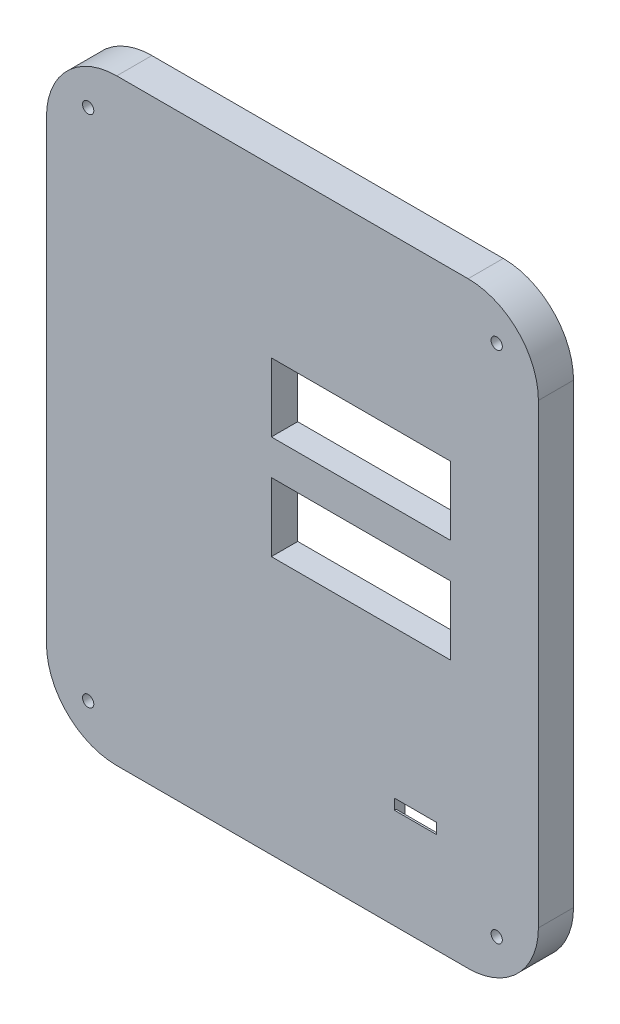
SolidWorks part; units mm, degrees
ref_plane "Front Plane" through (0, 0, 0) normal (0, 0, 1) x (1, 0, 0)
ref_plane "Top Plane" through (0, 0, 0) normal (0, 1, 0) x (1, 0, 0)
ref_plane "Right Plane" through (0, 0, 0) normal (1, 0, 0) x (0, 0, -1)
sketch "Sketch1" plane through (0, 0, 0) normal (0, 0, 1) x (1, 0, 0)
  line L0 (-47.1227, 101.0393) -> (52.8773, 101.0393) construction
  line L1 (72.8773, 81.0393) -> (72.8773, -48.9607) construction
  line L2 (-0.3727, -68.9607) -> (-47.1227, -68.9607) construction
  line L3 (-67.1227, -48.9607) -> (-67.1227, 81.0393) construction
  line L4 (-47.1227, 101.0393) -> (52.8773, 101.0393)
  line L5 (72.8773, 81.0393) -> (72.8773, -48.9607)
  line L6 (52.8773, -68.9607) -> (-47.1227, -68.9607)
  line L7 (-67.1227, -48.9607) -> (-67.1227, 81.0393)
  arc A0 (-47.1227, 101.0393) -> (-67.1227, 81.0393) centre (-47.1227, 81.0393) ccw construction
  arc A1 (72.8773, 81.0393) -> (52.8773, 101.0393) centre (52.8773, 81.0393) ccw construction
  arc A2 (52.8773, -68.9607) -> (72.8773, -48.9607) centre (52.8773, -48.9607) ccw construction
  arc A3 (-67.1227, -48.9607) -> (-47.1227, -68.9607) centre (-47.1227, -48.9607) ccw construction
  arc A4 (-47.1227, 101.0393) -> (-67.1227, 81.0393) centre (-47.1227, 81.0393) ccw
  arc A5 (72.8773, 81.0393) -> (52.8773, 101.0393) centre (52.8773, 81.0393) ccw
  arc A6 (52.8773, -68.9607) -> (72.8773, -48.9607) centre (52.8773, -48.9607) ccw
  arc A7 (-67.1227, -48.9607) -> (-47.1227, -68.9607) centre (-47.1227, -48.9607) ccw
extrude "Boss-Extrude1" add sketch "Sketch1" along normal blind 10
shell "Shell1" thickness 4 removed face at (2.8773, 16.0393, 0)
ref_plane "Plane1" through (0, 16.0393, 0) normal (0, 1, 0) x (1, 0, 0)
ref_plane "Plane2" through (2.8773, 0, 0) normal (1, 0, 0) x (0, 0, -1)
sketch "Sketch2" plane through (0, 0, 0) normal (0, 0, -1) x (-1, 0, 0)
  line L0 (47.89, 95.1878) -> (51.0972, 87.4483) construction
  line L1 (61.2712, 81.8066) -> (53.5317, 85.0139) construction
  line L2 (47.89, 95.1878) -> (51.0972, 87.4483)
  line L3 (61.2712, 81.8066) -> (53.5317, 85.0139)
  line L4 (-52.8773, 97.0393) -> (47.1227, 97.0393) construction
  line L5 (-52.8773, 97.0393) -> (47.1227, 97.0393)
  line L6 (63.1227, 81.0393) -> (63.1227, -48.9607) construction
  line L7 (63.1227, 81.0393) -> (63.1227, -48.9607)
  arc A0 (47.89, 95.1878) -> (45.1185, 97.0393) centre (45.1185, 94.0393) ccw construction
  arc A1 (51.0972, 87.4483) -> (53.5317, 85.0139) centre (55.2544, 89.1711) ccw construction
  arc A2 (63.1227, 79.0352) -> (61.2712, 81.8066) centre (60.1227, 79.0352) ccw construction
  arc A3 (47.89, 95.1878) -> (45.1185, 97.0393) centre (45.1185, 94.0393) ccw
  arc A4 (51.0972, 87.4483) -> (53.5317, 85.0139) centre (55.2544, 89.1711) ccw
  arc A5 (63.1227, 79.0352) -> (61.2712, 81.8066) centre (60.1227, 79.0352) ccw
  arc A6 (63.1227, 81.0393) -> (47.1227, 97.0393) centre (47.1227, 81.0393) ccw construction
  arc A7 (63.1227, 81.0393) -> (47.1227, 97.0393) centre (47.1227, 81.0393) ccw
  circle A8 centre (55.2544, 89.1711) radius 2.2 construction
  circle A9 centre (55.2544, 89.1711) radius 2.2 construction
  circle A10 centre (55.2544, 89.1711) radius 1.6
  arc M3 (47.1227, 97.0393) -> (63.1227, 81.0393) centre (47.1227, 81.0393) cw
  line M4 (63.1227, 81.0393) -> (63.1227, -48.9607)
  dimension "D1" = 3.2
extrude "Boss-Extrude2" add sketch "Sketch2" against normal up to surface (7 mm away) contours A5 L5 A3 L2 A4 L3 A10 M4 M3 | A10 region at (-46.9265, 96.7456, 0) region at (-55.2544, 89.1711, 0) up to face at (2.8773, 16.0393, 7)
extrude "Cut-Extrude1" cut sketch "Sketch2<3>" against normal through all contours A10 region at (-55.2544, 89.1711, 0)
sketch "Sketch2<3>" plane through (0, 0, 0) normal (0, 0, -1) x (-1, 0, 0) same geometry as "Sketch2"
mirror "Mirror6" about plane through (0, 16.0393, 0) normal (0, 1, 0) of "Cut-Extrude1", "Boss-Extrude2"
mirror "Mirror7" about plane through (2.8773, 0, 0) normal (1, 0, 0) of "Mirror6"
sketch "Sketch3" plane through (0, 0, 0) normal (0, 0, -1) x (-1, 0, 0)
  line L0 (63.1227, 79.0352) -> (63.1227, -46.9565) construction
  line L2 (61.2712, -49.7279) -> (53.5317, -52.9352) construction
  line L6 (47.89, -63.1092) -> (51.0972, -55.3696) construction
  line L12 (45.1185, -64.9607) -> (-50.8731, -64.9607) construction
  line L20 (-53.6446, -63.1092) -> (-56.8519, -55.3696) construction
  line L25 (-67.0258, -49.7279) -> (-59.2863, -52.9352) construction
  line L26 (-68.8773, -46.9565) -> (-68.8773, 79.0352) construction
  line L27 (-67.0258, 81.8066) -> (-59.2863, 85.0139) construction
  line L28 (-53.6446, 95.1878) -> (-56.8519, 87.4483) construction
  line L29 (-50.8731, 97.0393) -> (45.1185, 97.0393) construction
  line L30 (47.89, 95.1878) -> (51.0972, 87.4483) construction
  line L31 (61.2712, 81.8066) -> (53.5317, 85.0139) construction
  line L32 (45.1185, -64.9607) -> (-50.8731, -64.9607)
  line L33 (-53.6446, -63.1092) -> (-56.8519, -55.3696)
  line L34 (-67.0258, -49.7279) -> (-59.2863, -52.9352)
  line L35 (-68.8773, -46.9565) -> (-68.8773, 79.0352)
  line L36 (-67.0258, 81.8066) -> (-59.2863, 85.0139)
  line L37 (-53.6446, 95.1878) -> (-56.8519, 87.4483)
  line L38 (-50.8731, 97.0393) -> (45.1185, 97.0393)
  line L39 (47.89, 95.1878) -> (51.0972, 87.4483)
  line L40 (61.2712, 81.8066) -> (53.5317, 85.0139)
  line L41 (63.1227, 79.0352) -> (63.1227, -46.9565)
  line L42 (61.2712, -49.7279) -> (53.5317, -52.9352)
  line L43 (47.89, -63.1092) -> (51.0972, -55.3696)
  line L44 (45.1185, -64.4607) -> (-50.8731, -64.4607)
  line L45 (-53.1827, -62.9177) -> (-56.3899, -55.1782)
  line L46 (-66.8344, -49.266) -> (-59.0949, -52.4733)
  line L47 (-68.3773, -46.9565) -> (-68.3773, 79.0352)
  line L48 (-66.8344, 81.3447) -> (-59.0949, 84.552)
  line L49 (-53.1827, 94.9964) -> (-56.3899, 87.2569)
  line L50 (-50.8731, 96.5393) -> (45.1185, 96.5393)
  line L51 (47.4281, 94.9964) -> (50.6353, 87.2569)
  line L52 (61.0798, 81.3447) -> (53.3403, 84.552)
  line L53 (62.6227, 79.0352) -> (62.6227, -46.9565)
  line L54 (61.0798, -49.266) -> (53.3403, -52.4733)
  line L55 (47.4281, -62.9177) -> (50.6353, -55.1782)
  line L56 (45.1185, -62.4607) -> (-50.8731, -62.4607)
  line L57 (-51.335, -62.1521) -> (-54.5423, -54.4126)
  line L58 (-66.0687, -47.4184) -> (-58.3292, -50.6257)
  line L59 (-66.3773, -46.9565) -> (-66.3773, 79.0352)
  line L60 (-66.0687, 79.4971) -> (-58.3292, 82.7044)
  line L61 (-51.335, 94.2308) -> (-54.5423, 86.4912)
  line L62 (-50.8731, 94.5393) -> (45.1185, 94.5393)
  line L63 (45.5804, 94.2308) -> (48.7877, 86.4912)
  line L64 (60.3141, 79.4971) -> (52.5746, 82.7044)
  line L65 (60.6227, 79.0352) -> (60.6227, -46.9565)
  line L66 (60.3141, -47.4184) -> (52.5746, -50.6257)
  line L67 (45.5804, -62.1521) -> (48.7877, -54.4126)
  arc A0 (61.2712, -49.7279) -> (63.1227, -46.9565) centre (60.1227, -46.9565) ccw construction
  arc A2 (53.5317, -52.9352) -> (51.0972, -55.3696) centre (55.2544, -57.0924) ccw construction
  arc A6 (45.1185, -64.9607) -> (47.89, -63.1092) centre (45.1185, -61.9607) ccw construction
  arc A12 (-53.6446, -63.1092) -> (-50.8731, -64.9607) centre (-50.8731, -61.9607) ccw construction
  arc A20 (-56.8519, -55.3696) -> (-59.2863, -52.9352) centre (-61.009, -57.0924) ccw construction
  arc A21 (-68.8773, -46.9565) -> (-67.0258, -49.7279) centre (-65.8773, -46.9565) ccw construction
  arc A22 (-67.0258, 81.8066) -> (-68.8773, 79.0352) centre (-65.8773, 79.0352) ccw construction
  arc A23 (-59.2863, 85.0139) -> (-56.8519, 87.4483) centre (-61.009, 89.1711) ccw construction
  arc A24 (-50.8731, 97.0393) -> (-53.6446, 95.1878) centre (-50.8731, 94.0393) ccw construction
  arc A25 (47.89, 95.1878) -> (45.1185, 97.0393) centre (45.1185, 94.0393) ccw construction
  arc A26 (51.0972, 87.4483) -> (53.5317, 85.0139) centre (55.2544, 89.1711) ccw construction
  arc A27 (63.1227, 79.0352) -> (61.2712, 81.8066) centre (60.1227, 79.0352) ccw construction
  arc A28 (-53.6446, -63.1092) -> (-50.8731, -64.9607) centre (-50.8731, -61.9607) ccw
  arc A29 (-56.8519, -55.3696) -> (-59.2863, -52.9352) centre (-61.009, -57.0924) ccw
  arc A30 (-68.8773, -46.9565) -> (-67.0258, -49.7279) centre (-65.8773, -46.9565) ccw
  arc A31 (-67.0258, 81.8066) -> (-68.8773, 79.0352) centre (-65.8773, 79.0352) ccw
  arc A32 (-59.2863, 85.0139) -> (-56.8519, 87.4483) centre (-61.009, 89.1711) ccw
  arc A33 (-50.8731, 97.0393) -> (-53.6446, 95.1878) centre (-50.8731, 94.0393) ccw
  arc A34 (47.89, 95.1878) -> (45.1185, 97.0393) centre (45.1185, 94.0393) ccw
  arc A35 (51.0972, 87.4483) -> (53.5317, 85.0139) centre (55.2544, 89.1711) ccw
  arc A36 (63.1227, 79.0352) -> (61.2712, 81.8066) centre (60.1227, 79.0352) ccw
  arc A37 (61.2712, -49.7279) -> (63.1227, -46.9565) centre (60.1227, -46.9565) ccw
  arc A38 (53.5317, -52.9352) -> (51.0972, -55.3696) centre (55.2544, -57.0924) ccw
  arc A39 (45.1185, -64.9607) -> (47.89, -63.1092) centre (45.1185, -61.9607) ccw
  arc A40 (-53.1827, -62.9177) -> (-50.8731, -64.4607) centre (-50.8731, -61.9607) ccw
  arc A41 (-56.3899, -55.1782) -> (-59.0949, -52.4733) centre (-61.009, -57.0924) ccw
  arc A42 (-68.3773, -46.9565) -> (-66.8344, -49.266) centre (-65.8773, -46.9565) ccw
  arc A43 (-66.8344, 81.3447) -> (-68.3773, 79.0352) centre (-65.8773, 79.0352) ccw
  arc A44 (-59.0949, 84.552) -> (-56.3899, 87.2569) centre (-61.009, 89.1711) ccw
  arc A45 (-50.8731, 96.5393) -> (-53.1827, 94.9964) centre (-50.8731, 94.0393) ccw
  arc A46 (47.4281, 94.9964) -> (45.1185, 96.5393) centre (45.1185, 94.0393) ccw
  arc A47 (50.6353, 87.2569) -> (53.3403, 84.552) centre (55.2544, 89.1711) ccw
  arc A48 (62.6227, 79.0352) -> (61.0798, 81.3447) centre (60.1227, 79.0352) ccw
  arc A49 (61.0798, -49.266) -> (62.6227, -46.9565) centre (60.1227, -46.9565) ccw
  arc A50 (53.3403, -52.4733) -> (50.6353, -55.1782) centre (55.2544, -57.0924) ccw
  arc A51 (45.1185, -64.4607) -> (47.4281, -62.9177) centre (45.1185, -61.9607) ccw
  arc A52 (-51.335, -62.1521) -> (-50.8731, -62.4607) centre (-50.8731, -61.9607) ccw
  arc A53 (-54.5423, -54.4126) -> (-58.3292, -50.6257) centre (-61.009, -57.0924) ccw
  arc A54 (-66.3773, -46.9565) -> (-66.0687, -47.4184) centre (-65.8773, -46.9565) ccw
  arc A55 (-66.0687, 79.4971) -> (-66.3773, 79.0352) centre (-65.8773, 79.0352) ccw
  arc A56 (-58.3292, 82.7044) -> (-54.5423, 86.4912) centre (-61.009, 89.1711) ccw
  arc A57 (-50.8731, 94.5393) -> (-51.335, 94.2308) centre (-50.8731, 94.0393) ccw
  arc A58 (45.5804, 94.2308) -> (45.1185, 94.5393) centre (45.1185, 94.0393) ccw
  arc A59 (48.7877, 86.4912) -> (52.5746, 82.7044) centre (55.2544, 89.1711) ccw
  arc A60 (60.6227, 79.0352) -> (60.3141, 79.4971) centre (60.1227, 79.0352) ccw
  arc A61 (60.3141, -47.4184) -> (60.6227, -46.9565) centre (60.1227, -46.9565) ccw
  arc A62 (52.5746, -50.6257) -> (48.7877, -54.4126) centre (55.2544, -57.0924) ccw
  arc A63 (45.1185, -62.4607) -> (45.5804, -62.1521) centre (45.1185, -61.9607) ccw
  arc M4 (-53.6446, 95.1878) -> (-50.8731, 97.0393) centre (-50.8731, 94.0393) cw
  line M5 (-50.8731, 97.0393) -> (45.1185, 97.0393)
  arc M6 (45.1185, 97.0393) -> (47.89, 95.1878) centre (45.1185, 94.0393) cw
  line M7 (47.89, 95.1878) -> (51.0972, 87.4483)
  arc M8 (51.0972, 87.4483) -> (53.5317, 85.0139) centre (55.2544, 89.1711) ccw
  line M9 (53.5317, 85.0139) -> (61.2712, 81.8066)
  arc M10 (61.2712, 81.8066) -> (63.1227, 79.0352) centre (60.1227, 79.0352) cw
  line M11 (63.1227, 79.0352) -> (63.1227, -46.9565)
  arc M12 (63.1227, -46.9565) -> (61.2712, -49.7279) centre (60.1227, -46.9565) cw
  line M13 (61.2712, -49.7279) -> (53.5317, -52.9352)
  arc M14 (53.5317, -52.9352) -> (51.0972, -55.3696) centre (55.2544, -57.0924) ccw
  line M15 (51.0972, -55.3696) -> (47.89, -63.1092)
  arc M16 (47.89, -63.1092) -> (45.1185, -64.9607) centre (45.1185, -61.9607) cw
  line M17 (45.1185, -64.9607) -> (-50.8731, -64.9607)
  arc M18 (-50.8731, -64.9607) -> (-53.6446, -63.1092) centre (-50.8731, -61.9607) cw
  line M19 (-53.6446, -63.1092) -> (-56.8519, -55.3696)
  arc M20 (-56.8519, -55.3696) -> (-59.2863, -52.9352) centre (-61.009, -57.0924) ccw
  line M21 (-59.2863, -52.9352) -> (-67.0258, -49.7279)
  arc M22 (-67.0258, -49.7279) -> (-68.8773, -46.9565) centre (-65.8773, -46.9565) cw
  line M23 (-68.8773, -46.9565) -> (-68.8773, 79.0352)
  arc M24 (-68.8773, 79.0352) -> (-67.0258, 81.8066) centre (-65.8773, 79.0352) cw
  line M25 (-67.0258, 81.8066) -> (-59.2863, 85.0139)
  arc M26 (-59.2863, 85.0139) -> (-56.8519, 87.4483) centre (-61.009, 89.1711) ccw
  line M27 (-56.8519, 87.4483) -> (-53.6446, 95.1878)
  dimension "D1" = 0.5
  dimension "D2" = 2
extrude "Boss-Extrude3" add sketch "Sketch3" against normal up to surface (7 mm away) contours L44 A51 L55 A50 L54 A49 L53 A48 L52 A47 L51 A46 L50 A45 L49 A44 L48 A43 L47 A42 L46 A41 L45 A40 A63 L56 A52 L57 A53 L58 A54 L59 A55 L60 A56 L61 A57 L62 A58 L63 A59 L64 A60 L65 A61 L66 A62 L67 | A51 L44 A40 L45 A41 L46 A42 L47 A43 L48 A44 L49 A45 L50 A46 L51 A47 L52 A48 L53 A49 L54 A50 L55 M4 M27 M26 M25 M24 M23 M22 M21 M20 M19 M18 M17 M16 M15 M14 M13 M12 M11 M10 M9 M8 M7 M6 M5 region at (2.8773, -64.7517, 0) region at (2.8773, -64.2531, 0) up to face at (2.8773, 16.0393, 7)
extrude "Boss-Extrude4" add sketch "Sketch3<3>" along normal blind 2 contours L44 A51 L55 A50 L54 A49 L53 A48 L52 A47 L51 A46 L50 A45 L49 A44 L48 A43 L47 A42 L46 A41 L45 A40 A63 L56 A52 L57 A53 L58 A54 L59 A55 L60 A56 L61 A57 L62 A58 L63 A59 L64 A60 L65 A61 L66 A62 L67 region at (2.8773, -64.2531, 0)
sketch "Sketch3<3>" plane through (0, 0, 0) normal (0, 0, -1) x (-1, 0, 0) same geometry as "Sketch3"
sketch "Sketch4" plane through (0, 0, 7) normal (0, 0, -1) x (-1, 0, 0)
  line L0 (-22.3773, 14.2893) -> (-22.3773, 43.7893) construction
  line L1 (-47.8773, 4.5393) -> (3.1227, 4.5393)
  line L2 (-47.8773, 4.5393) -> (-47.8773, 24.0393)
  line L3 (-47.8773, 24.0393) -> (3.1227, 24.0393)
  line L4 (3.1227, 4.5393) -> (3.1227, 24.0393)
  line L5 (-47.8773, 4.5393) -> (3.1227, 24.0393) construction
  line L6 (-47.8773, 24.0393) -> (3.1227, 4.5393) construction
  line L7 (-47.8773, 34.0393) -> (3.1227, 34.0393)
  line L8 (-47.8773, 34.0393) -> (-47.8773, 53.5393)
  line L9 (-47.8773, 53.5393) -> (3.1227, 53.5393)
  line L10 (3.1227, 34.0393) -> (3.1227, 53.5393)
  line L11 (-47.8773, 34.0393) -> (3.1227, 53.5393) construction
  line L12 (-47.8773, 53.5393) -> (3.1227, 34.0393) construction
  line L13 (-24.3773, -1.0607) -> (61.6227, -1.0607) construction
  line L14 (-24.3773, -1.0607) -> (61.6227, -1.0607) construction
  line L15 (-72.8773, -48.9607) -> (-72.8773, 81.0393) construction
  line L17 (-52.8773, 101.0393) -> (47.1227, 101.0393) construction
  point P0 (-22.3773, 14.2893)
  point P5 (-22.3773, 43.7893)
  dimension "D1" = 19.5
  dimension "D2" = 51
  dimension "D3" = 10
  dimension "D4" = 47.5
  dimension "D5" = 25
extrude "Cut-Extrude2" cut sketch "Sketch4" against normal through all
sketch "Sketch5" plane through (0, 0, 7) normal (0, 0, -1) x (-1, 0, 0)
  line L0 (3.1227, 4.5393) -> (3.1227, 24.0393) construction
  line L1 (3.1227, 24.0393) -> (-47.8773, 24.0393) construction
  line L2 (-47.8773, 24.0393) -> (-47.8773, 4.5393) construction
  line L3 (-47.8773, 4.5393) -> (3.1227, 4.5393) construction
  line L4 (3.1227, 4.5393) -> (3.1227, 24.0393)
  line L5 (3.1227, 24.0393) -> (-47.8773, 24.0393)
  line L6 (-47.8773, 24.0393) -> (-47.8773, 4.5393)
  line L7 (-47.8773, 4.5393) -> (3.1227, 4.5393)
  line L8 (8.0227, 27.8893) -> (-55.9773, 27.8893) construction
  line L9 (9.0227, 1.6893) -> (9.0227, 26.8893) construction
  line L10 (-55.9773, 0.6893) -> (8.0227, 0.6893) construction
  line L11 (-56.9773, 26.8893) -> (-56.9773, 1.6893) construction
  line L12 (8.0227, 27.8893) -> (-55.9773, 27.8893)
  line L13 (9.0227, 1.6893) -> (9.0227, 26.8893)
  line L14 (-55.9773, 0.6893) -> (8.0227, 0.6893)
  line L15 (-56.9773, 26.8893) -> (-56.9773, 1.6893)
  arc A0 (-55.9773, 27.8893) -> (-56.9773, 26.8893) centre (-55.9773, 26.8893) ccw construction
  arc A1 (9.0227, 26.8893) -> (8.0227, 27.8893) centre (8.0227, 26.8893) ccw construction
  arc A2 (8.0227, 0.6893) -> (9.0227, 1.6893) centre (8.0227, 1.6893) ccw construction
  arc A3 (-56.9773, 1.6893) -> (-55.9773, 0.6893) centre (-55.9773, 1.6893) ccw construction
  arc A4 (-55.9773, 27.8893) -> (-56.9773, 26.8893) centre (-55.9773, 26.8893) ccw
  arc A5 (9.0227, 26.8893) -> (8.0227, 27.8893) centre (8.0227, 26.8893) ccw
  arc A6 (8.0227, 0.6893) -> (9.0227, 1.6893) centre (8.0227, 1.6893) ccw
  arc A7 (-56.9773, 1.6893) -> (-55.9773, 0.6893) centre (-55.9773, 1.6893) ccw
  arc A8 (4.5747, 24.2483) -> (7.4707, 25.8304) centre (6.0227, 25.0393) ccw construction
  arc A9 (4.5747, 24.2483) -> (7.4707, 25.8304) centre (6.0227, 25.0393) ccw construction
  arc A10 (7.4707, 25.8304) -> (4.5747, 24.2483) centre (6.0227, 25.0393) ccw construction
  arc A11 (7.4707, 25.8304) -> (4.5747, 24.2483) centre (6.0227, 25.0393) ccw construction
  arc A12 (4.5747, 2.7483) -> (7.4707, 4.3304) centre (6.0227, 3.5393) ccw construction
  arc A13 (7.4707, 4.3304) -> (4.5747, 2.7483) centre (6.0227, 3.5393) ccw construction
  arc A14 (4.5747, 2.7483) -> (7.4707, 4.3304) centre (6.0227, 3.5393) ccw construction
  arc A15 (7.4707, 4.3304) -> (4.5747, 2.7483) centre (6.0227, 3.5393) ccw construction
  arc A16 (-52.5293, 4.3304) -> (-55.4253, 2.7483) centre (-53.9773, 3.5393) ccw construction
  arc A17 (-55.4253, 2.7483) -> (-52.5293, 4.3304) centre (-53.9773, 3.5393) ccw construction
  arc A18 (-52.5293, 4.3304) -> (-55.4253, 2.7483) centre (-53.9773, 3.5393) ccw construction
  arc A19 (-55.4253, 2.7483) -> (-52.5293, 4.3304) centre (-53.9773, 3.5393) ccw construction
  arc A20 (-52.5293, 25.8304) -> (-55.4253, 24.2483) centre (-53.9773, 25.0393) ccw construction
  arc A21 (-55.4253, 24.2483) -> (-52.5293, 25.8304) centre (-53.9773, 25.0393) ccw construction
  arc A22 (-52.5293, 25.8304) -> (-55.4253, 24.2483) centre (-53.9773, 25.0393) ccw construction
  arc A23 (-55.4253, 24.2483) -> (-52.5293, 25.8304) centre (-53.9773, 25.0393) ccw construction
  circle A24 centre (6.0227, 25.0393) radius 2.2
  circle A25 centre (6.0227, 3.5393) radius 2.2
  circle A26 centre (-53.9773, 25.0393) radius 2.2
  circle A27 centre (-53.9773, 3.5393) radius 2.2
  line M17 (-47.8773, 24.0393) -> (3.1227, 24.0393)
  line M18 (3.1227, 24.0393) -> (3.1227, 4.5393)
  line M19 (3.1227, 4.5393) -> (-47.8773, 4.5393)
  line M20 (-47.8773, 4.5393) -> (-47.8773, 24.0393)
  dimension "D1" = 4.4
extrude "Boss-Extrude5" add sketch "Sketch5" along normal blind 4.5 contours L15 A7 L14 A6 L13 A5 L12 A4 A27 A26 A25 A24 M20 M17 M18 M19 | A25 | A24 | A26 | A27 region at (-8.225, 27.0917, 7) region at (-6.0227, 25.0393, 7) region at (-6.0227, 3.5393, 7) region at (53.9773, 25.0393, 7) region at (53.9773, 3.5393, 7)
sketch "Sketch6" plane through (0, 0, 2.5) normal (0, 0, -1) x (-1, 0, 0)
  line L0 (-52.1473, 8.5993) -> (-49.4073, 8.5993) construction
  line L1 (-52.1473, 18.9593) -> (-52.1473, 8.5993) construction
  line L2 (-49.4073, 18.9593) -> (-52.1473, 18.9593) construction
  line L3 (-49.4073, 8.5993) -> (-49.4073, 18.9593) construction
  line L4 (-49.4073, 18.9593) -> (-52.1473, 18.9593)
  line L5 (-49.4073, 8.5993) -> (-49.4073, 18.9593)
  line L6 (-52.1473, 8.5993) -> (-49.4073, 8.5993)
  line L7 (-52.1473, 18.9593) -> (-52.1473, 8.5993)
  line L8 (7.3927, 18.9593) -> (4.6527, 18.9593) construction
  line L9 (4.6527, 18.9593) -> (4.6527, 8.5993) construction
  line L10 (4.6527, 8.5993) -> (7.3927, 8.5993) construction
  line L11 (7.3927, 8.5993) -> (7.3927, 18.9593) construction
  line L12 (7.3927, 18.9593) -> (4.6527, 18.9593)
  line L13 (4.6527, 18.9593) -> (4.6527, 8.5993)
  line L14 (4.6527, 8.5993) -> (7.3927, 8.5993)
  line L15 (7.3927, 8.5993) -> (7.3927, 18.9593)
extrude "Cut-Extrude3" cut sketch "Sketch6" against normal blind 3
extrude "Cut-Extrude4" cut sketch "Sketch5<3>" against normal blind 4.5 from surface contours A25 | A24 | A26 | A27 region at (-6.0227, 25.0393, 7) region at (-6.0227, 3.5393, 7) region at (53.9773, 25.0393, 7) region at (53.9773, 3.5393, 7) starting at face at (50.7773, 13.7793, 2.5)
sketch "Sketch5<3>" plane through (0, 0, 7) normal (0, 0, -1) x (-1, 0, 0) same geometry as "Sketch5"
chamfer "Chamfer1" distance 0.5 angle 45 4 edges at (-8.2227, 25.0393, 2.5) (-8.2227, 3.5393, 2.5) (51.7773, 3.5393, 2.5) (51.7773, 25.0393, 2.5)
pattern_sketch "Sketch-Pattern1" of "Chamfer1", "Cut-Extrude4", "Cut-Extrude3", "Boss-Extrude5" driven by "Sketch4"
sketch "Sketch7" plane through (0, 0, 7) normal (0, 0, -1) x (-1, 0, 0)
  line L0 (-72.8773, -48.9607) -> (-72.8773, 81.0393) construction
  line L1 (-31.8773, -37.4607) -> (-43.8773, -37.4607)
  line L2 (-31.8773, -37.4607) -> (-31.8773, -52.4607)
  line L3 (-31.8773, -52.4607) -> (-43.8773, -52.4607)
  line L4 (-43.8773, -37.4607) -> (-43.8773, -52.4607)
  line L5 (-31.8773, -37.4607) -> (-43.8773, -52.4607) construction
  line L6 (-31.8773, -52.4607) -> (-43.8773, -37.4607) construction
  line L7 (47.1227, -68.9607) -> (-52.8773, -68.9607) construction
  line L9 (-43.8773, -37.4607) -> (-31.8773, -37.4607)
  line L10 (-43.8773, -37.4607) -> (-43.8773, -40.4607)
  line L11 (-43.8773, -40.4607) -> (-31.8773, -40.4607)
  line L12 (-31.8773, -37.4607) -> (-31.8773, -40.4607)
  point P0 (-37.8773, -44.9607)
  dimension "D1" = 35
  dimension "D2" = 24
  dimension "D3" = 15
  dimension "D4" = 12
  dimension "D5" = 3
extrude "Cut-Extrude5" cut sketch "Sketch7" against normal offset from surface (2.5 mm away) 0.5 contours L11 L4 L3 L2 region at (37.8773, -46.4607, 7) up to face at (22.3773, 14.2893, 10)
extrude "Cut-Extrude6" cut sketch "Sketch7<3>" against normal through all contours L4 L11 L2 L1 region at (37.8773, -38.9607, 7)
sketch "Sketch7<3>" plane through (0, 0, 7) normal (0, 0, -1) x (-1, 0, 0) same geometry as "Sketch7"
